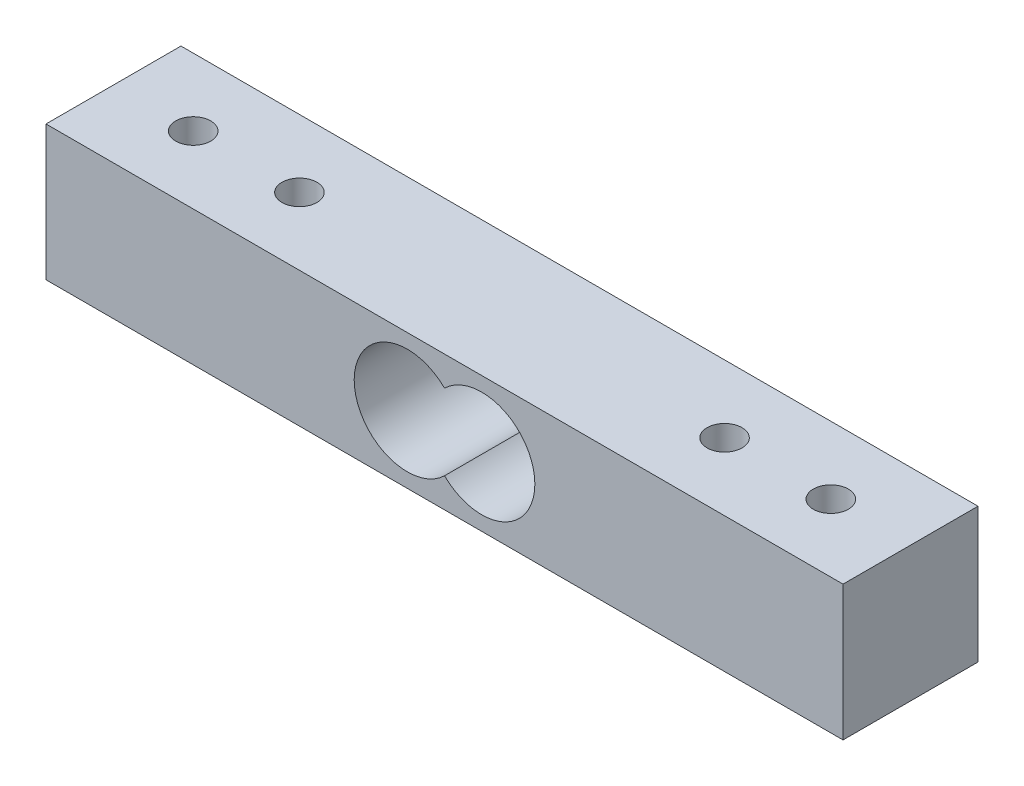
SolidWorks part; units mm, degrees
ref_plane "Ebene vorne" through (0, 0, 0) normal (0, 0, 1) x (1, 0, 0)
ref_plane "Ebene oben" through (0, 0, 0) normal (0, 1, 0) x (1, 0, 0)
ref_plane "Ebene rechts" through (0, 0, 0) normal (1, 0, 0) x (0, 0, -1)
sketch "Skizze2" plane through (0, 0, 0) normal (0, 1, 0) x (1, 0, 0)
  line L1 (-37.5, -6.35) -> (37.5, -6.35)
  line L2 (-37.5, -6.35) -> (-37.5, 6.35)
  line L3 (-37.5, 6.35) -> (37.5, 6.35)
  line L4 (37.5, -6.35) -> (37.5, 6.35)
  line L5 (-37.5, -6.35) -> (37.5, 6.35) construction
  line L6 (-37.5, 6.35) -> (37.5, -6.35) construction
  line L8 (-55, 0) -> (55, 0) construction
  line L9 (0, -55) -> (0, 55) construction
  circle A2 centre (-20, 0) radius 1.65
  circle A3 centre (-30, 0) radius 1.65
  circle A4 centre (20, 0) radius 1.65
  circle A5 centre (30, 0) radius 1.65
  point P0 (0, 0)
  dimension "D3" = 12.7
  dimension "D4" = 30
  dimension "D1" = 20
  dimension "D2" = 75
extrude "Aufsatz-Linear austragen1" add sketch "Skizze2" along normal blind 6.35 and the other way blind 6.35
sketch "Skizze3" plane through (0, 0, 0) normal (0, 0, 1) x (1, 0, 0)
  line L0 (6.985, 0) -> (-6.985, 0) construction
  line L1 (0, -6.985) -> (0, 6.985) construction
  arc A0 (0, 3.5707) -> (0, -3.5707) centre (-3.5, 0) ccw
  arc A1 (0, 3.5707) -> (0, -3.5707) centre (3.5, 0) cw
  dimension "D1" = 10
  dimension "D2" = 3.5
extrude "Schnitt-Linear austragen2" cut sketch "Skizze3" along direction (0, 0, 1) on the side against the normal through all both and the other way through all
ref_plane "Ebene1" through (0, 0, 0) normal (0, 1, 0) x (1, 0, 0)
sketch "Skizze4" plane through (0, 0, 0) normal (0, 1, 0) x (1, 0, 0)
  line L4 (-37.5, -6.35) -> (37.5, -6.35)
  line L5 (-37.5, -6.35) -> (-37.5, 6.35)
  line L6 (-37.5, 6.35) -> (37.5, 6.35)
  line L7 (37.5, -6.35) -> (37.5, 6.35)
  line L8 (-37.5, -6.35) -> (37.5, 6.35) construction
  line L9 (-37.5, 6.35) -> (37.5, -6.35) construction
  circle A0 centre (20, 0) radius 1.65
  circle A1 centre (30, 0) radius 1.65
  circle A2 centre (-30, 0) radius 1.65
  circle A3 centre (-20, 0) radius 1.65
  point P8 (0, 0)
